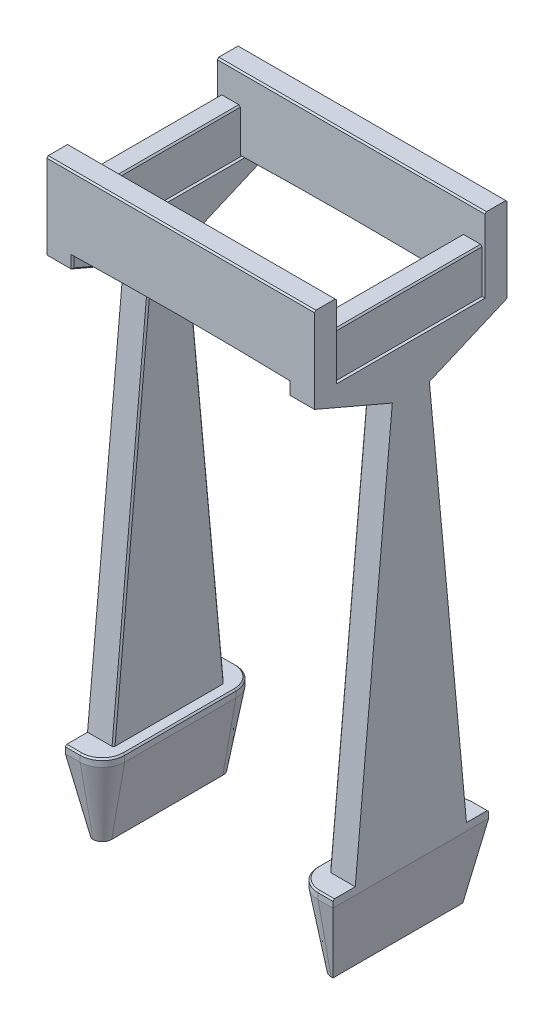
SolidWorks part; units mm, degrees
ref_plane "Front Plane" through (0, 0, 0) normal (0, 0, 1) x (1, 0, 0)
ref_plane "Top Plane" through (0, 0, 0) normal (0, 1, 0) x (1, 0, 0)
ref_plane "Right Plane" through (0, 0, 0) normal (1, 0, 0) x (0, 0, -1)
sketch "Sketch1" plane through (0, 0, 0) normal (0, 0, 1) x (1, 0, 0)
  line L0 (0, 0) -> (361.02, 0)
  line L1 (0, 0) -> (0, -100)
  line L2 (0, -100) -> (35, -100)
  line L3 (361.02, 0) -> (361.02, -100)
  line L4 (361.02, -100) -> (326.02, -100)
  arc A0 (35, -100) -> (326.02, -100) centre (180.51, -6098.2353) cw
  dimension "D4" = 6000
  dimension "D1" = 361.02
  dimension "D2" = 100
  dimension "D3" = 35
extrude "Boss-Extrude1" add sketch "Sketch1" along normal blind 30
sketch "Sketch2" plane through (0, 0, 0) normal (0, 0, -1) x (-1, 0, 0)
  line L0 (-343.52, -100) -> (-343.52, -40) construction
  line L1 (-326.02, -100) -> (-361.02, -100) construction
  line L2 (-17.5, -100) -> (-17.5, -40) construction
  line L3 (0, -100) -> (-35, -100) construction
  line L4 (-180.51, 0) -> (-180.51, -150) construction
  line L5 (-356.9835, -100) -> (-330.0565, -100)
  line L6 (-356.9835, -100) -> (-356.9835, -40)
  line L7 (-356.9835, -40) -> (-330.0565, -40)
  line L8 (-330.0565, -100) -> (-330.0565, -40)
  line L9 (-356.9835, -100) -> (-330.0565, -40) construction
  line L10 (-356.9835, -40) -> (-330.0565, -100) construction
  line L11 (-361.02, 0) -> (0, 0) construction
  line L12 (-4.0365, -40) -> (-30.9635, -40)
  line L13 (-30.9635, -100) -> (-30.9635, -40)
  line L14 (-4.0365, -100) -> (-30.9635, -100)
  line L15 (-4.0365, -100) -> (-4.0365, -40)
  point P8 (-343.52, -70)
  dimension "D1" = 60
  dimension "D2" = 26.927
  dimension "D3" = 150
extrude "Boss-Extrude2" add sketch "Sketch2" along normal blind 200
sketch "Sketch3" plane through (0, 0, -200) normal (0, 0, -1) x (-1, 0, 0)
  line L5 (0, -100) -> (0, 0)
  line L6 (-35, -100) -> (0, -100)
  line L7 (-361.02, -100) -> (-326.02, -100)
  line L8 (-361.02, 0) -> (-361.02, -100)
  line L9 (0, 0) -> (-361.02, 0)
  line L10 (0, -100) -> (0, 0)
  line L11 (-35, -100) -> (0, -100)
  line L12 (-361.02, -100) -> (-326.02, -100)
  line L13 (-361.02, 0) -> (-361.02, -100)
  line L14 (0, 0) -> (-361.02, 0)
  arc A1 (-35, -100) -> (-326.02, -100) centre (-180.51, -6098.2353) ccw
  arc A2 (-35, -100) -> (-326.02, -100) centre (-180.51, -6098.2353) ccw
  dimension "D1" = 0
extrude "Boss-Extrude3" add sketch "Sketch3" along normal blind 30
sketch "Sketch5" plane through (4.0365, 0, 0) normal (-1, 0, 0) x (0, 0, 1)
  line L0 (-200, -100) -> (0, -100) construction
  line L1 (-200, -100) -> (0, -100)
  line L2 (-200, -100) -> (-230, -100)
  line L3 (-230, -100) -> (-230, -115)
  line L4 (-230, -115) -> (-125, -160)
  line L5 (0, -100) -> (30, -100)
  line L6 (30, -100) -> (30, -115)
  line L7 (30, -115) -> (-75, -160)
  line L8 (-100, -100) -> (-100, -700) construction
  line L9 (-100, -700) -> (-25, -700)
  line L10 (-25, -700) -> (-75, -160)
  line L11 (-100, -700) -> (-175, -700)
  line L12 (-175, -700) -> (-125, -160)
  line L13 (-125, -160) -> (-75, -160) construction
  dimension "D1" = 600
  dimension "D2" = 75
  dimension "D3" = 75
  dimension "D4" = 60
  dimension "D5" = 15
  dimension "D6" = 50
extrude "Boss-Extrude4" add sketch "Sketch5" along normal up to surface (4.0365 mm away) and the other way up to vertex (30.9635 mm away) up to face at (0, -50, -215) other way up to point (35, -100, -200)
sketch "Sketch6" plane through (0, -700, 0) normal (0, -1, 0) x (1, 0, 0)
  line L0 (0, -25) -> (0, 5)
  line L1 (0, 5) -> (50, 5)
  line L2 (50, 5) -> (50, -205)
  line L3 (50, -205) -> (0, -205)
  line L4 (0, -205) -> (0, -175)
  line L5 (0, -175) -> (0, -25)
  dimension "D1" = 50
  dimension "D2" = 30
extrude "Boss-Extrude5" add sketch "Sketch6" along normal blind 10
fillet "Fillet1" radius 30 2 edges at (50, -705, -205) (50, -705, 5)
ref_plane "Plane1" through (180.51, 0, 0) normal (1, 0, 0) x (0, 0, -1)
sketch "Sketch7" plane through (180.51, 0, 0) normal (1, 0, 0) x (0, 0, -1)
  line L0 (230, 0) -> (230, -100) construction
  line L1 (-30, 0) -> (230, 0)
  line L2 (-30, 0) -> (-30, -710)
  line L3 (-30, -710) -> (230, -710)
  line L4 (230, 0) -> (230, -710)
  line L5 (175, -710) -> (25, -710) construction
extrude "Cut-Extrude1" cut sketch "Sketch7" along normal through all
mirror "Mirror2" about plane through (180.51, 0, 0) normal (1, 0, 0) of bodies 106
chamfer "Chamfer1" distance 2 angle 45 4 edges at (180.51, 0, -230) (180.51, 0, -200) (180.51, 0, 0) (180.51, 0, 30)
chamfer "Chamfer2" distance 2 angle 45 4 edges at (4.0365, -40, -100) (30.9635, -40, -100) (330.0565, -40, -100) (356.9835, -40, -100)
chamfer "Chamfer3" distance 2 angle 45 12 edges at (326.02, -107.5, 30) (326.02, -137.5, -22.5) (326.02, -430, -50) (326.02, -107.5, -230) (326.02, -137.5, -177.5) (326.02, -430, -150) (35, -107.5, -230) (35, -137.5, -177.5) (35, -430, -150) (35, -430, -50) (35, -137.5, -22.5) (35, -107.5, 30)
chamfer "Chamfer4" distance 2 angle 45 10 edges at (10, -700, 5) (41.2132, -700, -3.7868) (50, -700, -100) (41.2132, -700, -196.2132) (10, -700, -205) (351.02, -700, 5) (319.8068, -700, -3.7868) (311.02, -700, -100) (319.8068, -700, -196.2132) (351.02, -700, -205)
chamfer "Chamfer6" distance 2 angle 45 4 edges at (180.51, -98.2353, 30) (180.51, -98.2353, 0) (180.51, -98.2353, -200) (180.51, -98.2353, -230)
sketch "Sketch9" plane through (0, 0, 0) normal (0, 1, 0) x (1, 0, 0)
  line L0 (0, 215) -> (361.02, 215)
  line L1 (0, 228) -> (0, 202) construction
  line L2 (361.02, 228) -> (361.02, 202) construction
  line L3 (361.02, -15) -> (0, -15)
  line L4 (361.02, -28) -> (361.02, -2) construction
  line L5 (0, -28) -> (0, -2) construction
sketch "Sketch10" plane through (0, -710, 0) normal (0, -1, 0) x (1, 0, 0)
  line L0 (341.02, -205) -> (361.02, -205) construction
  line L1 (361.02, -205) -> (361.02, 5) construction
  line L2 (361.02, 5) -> (341.02, 5) construction
  line L3 (311.02, -25) -> (311.02, -175) construction
  line L4 (0, -205) -> (20, -205) construction
  line L5 (50, -175) -> (50, -25) construction
  line L6 (20, 5) -> (0, 5) construction
  line L7 (0, 5) -> (0, -205) construction
  line L8 (341.02, -205) -> (361.02, -205)
  line L9 (361.02, -205) -> (361.02, 5)
  line L10 (361.02, 5) -> (341.02, 5)
  line L11 (311.02, -25) -> (311.02, -175)
  line L12 (0, -205) -> (20, -205)
  line L13 (50, -175) -> (50, -25)
  line L14 (20, 5) -> (0, 5)
  line L15 (0, 5) -> (0, -205)
  arc A0 (341.02, 5) -> (311.02, -25) centre (341.02, -25) ccw construction
  arc A1 (311.02, -175) -> (341.02, -205) centre (341.02, -175) ccw construction
  arc A2 (20, -205) -> (50, -175) centre (20, -175) ccw construction
  arc A3 (50, -25) -> (20, 5) centre (20, -25) ccw construction
  arc A4 (341.02, 5) -> (311.02, -25) centre (341.02, -25) ccw
  arc A5 (311.02, -175) -> (341.02, -205) centre (341.02, -175) ccw
  arc A6 (20, -205) -> (50, -175) centre (20, -175) ccw
  arc A7 (50, -25) -> (20, 5) centre (20, -25) ccw
extrude "Boss-Extrude6" add sketch "Sketch10" along normal blind 99 draft 10
